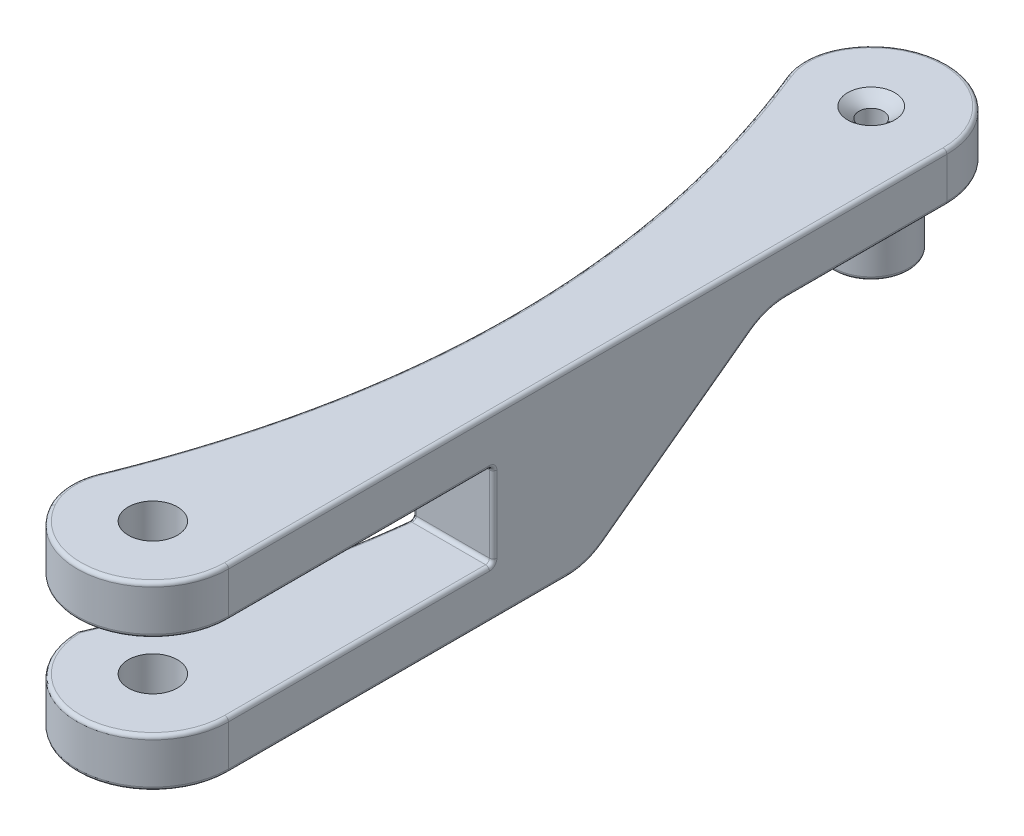
SolidWorks part; units mm, degrees
ref_plane "Front Plane" through (0, 0, 0) normal (0, 0, 1) x (1, 0, 0)
ref_plane "Top Plane" through (0, 0, 0) normal (0, 1, 0) x (1, 0, 0)
ref_plane "Right Plane" through (0, 0, 0) normal (1, 0, 0) x (0, 0, -1)
sketch "Sketch2" plane through (0, 0, 0) normal (0, 1, 0) x (1, 0, 0)
  line L0 (0, 0) -> (0, -95) construction
  line L1 (10, 0) -> (10, -95)
  line L2 (-10, 0) -> (-10, -95)
  arc A0 (10, 0) -> (-10, 0) centre (0, 0) ccw
  arc A1 (-10, -95) -> (10, -95) centre (0, -95) ccw
  circle A2 centre (0, 0) radius 1.625
  circle A3 centre (0, -95) radius 3.25
  point P3 (0, -47.5)
  dimension "D2" = 20
  dimension "D3" = 3.25
  dimension "D4" = 6.5
  dimension "D1" = 95
extrude "Boss-Extrude1" add sketch "Sketch2" along normal blind 16.5
sketch "Sketch3" plane through (0, 0, 0) normal (0, -1, 0) x (1, 0, 0)
  circle A0 centre (0, 0) radius 3.125
  dimension "D1" = 6.25
extrude "Cut-Extrude1" cut sketch "Sketch3" against normal blind 4.25
sketch "Sketch5" plane through (0, 0, 0) normal (0, -1, 0) x (1, 0, 0)
  line L0 (-10, 0) -> (-10, 47.5)
  line L1 (-10, 0) -> (-10, 95) construction
  line L2 (-10, 47.5) -> (10, 47.5)
  line L4 (10, 47.5) -> (10, 0)
  line L5 (10, 95) -> (10, 0) construction
  arc A0 (-10, 0) -> (10, 0) centre (0, 0) ccw
  arc A1 (-10, 0) -> (10, 0) centre (0, 0) ccw construction
  circle A2 centre (0, 0) radius 5
  dimension "D1" = 10
extrude "Cut-Extrude3" cut sketch "Sketch5" against normal blind 10.1
sketch "Sketch10" plane through (0, 0, 0) normal (0, -1, 0) x (1, 0, 0)
  line L0 (-10, 47.5) -> (10, 47.5)
  line L5 (-10, 47.5) -> (-10, 95)
  line L6 (10, 95) -> (10, 47.5)
  line L7 (-10, 47.5) -> (-10, 95)
  line L8 (10, 95) -> (10, 47.5)
  circle A1 centre (0, 95) radius 3.25
  arc A2 (10, 95) -> (-10, 95) centre (0, 95) ccw
  arc A3 (10, 95) -> (-10, 95) centre (0, 95) ccw
  circle A4 centre (0, 95) radius 3.25 construction
  dimension "D1" = 0
extrude "Boss-Extrude3" add sketch "Sketch10" along normal blind 7.4
sketch "Sketch8" plane through (10, 0, 0) normal (1, 0, 0) x (0, 0, -1)
  line L0 (-47.5, -7.4) -> (-23.75, 10.1)
  line L1 (0, 10.1) -> (-47.5, 10.1) construction
  line L2 (-23.75, 10.1) -> (-47.5, 10.1)
  line L3 (-47.5, 10.1) -> (-47.5, -7.4)
extrude "Boss-Extrude2" add sketch "Sketch8" against normal up to surface (20 mm away) up to face at (-10, 6.4, 47.5)
sketch "Sketch4" plane through (0, 16.5, 0) normal (0, 1, 0) x (1, 0, 0)
  line L0 (-10, 0) -> (-10, -95) construction
  line L1 (-10, 0) -> (-10, -95)
  spline S0 degree 2 poles (-10, 0) (10, -47.5) (-10, -95) knots 0 0 0 1 1 1
  point P8 (-10, -47.5)
extrude "Cut-Extrude2" cut sketch "Sketch4" against normal through all
sketch "Sketch9" plane through (0, 0, 0) normal (1, 0, 0) x (0, 0, -1)
  line L0 (-105, 16.5) -> (-105, -7.4) construction
  line L1 (-105, 10.1) -> (-60, 10.1)
  line L2 (-105, 10.1) -> (-105, -1)
  line L3 (-105, -1) -> (-60, -1)
  line L4 (-60, 10.1) -> (-60, -1)
  point P4 (-105, 4.55)
  dimension "D1" = 11.1
  dimension "D2" = 45
extrude "Cut-Extrude4" cut sketch "Sketch9" against normal through all both and the other way through all
fillet "Fillet1" radius 8 4 edges at (-10, 13.3, 95) (3.75, 10.1, 23.75) (5, -7.4, 47.5)
fillet "Fillet2" radius 0.5 33 edges at (10, 4.55, 60) (10, 10.1, 77.5) (2.5098, 10.1, 104.6799) (-9.7326, 10.1, 96.4681) (-0.6925, 4.55, 60) (4.6537, 10.1, 60) (0, -1, 105) (10, -1, 77.5) (4.6537, -1, 60) (10, 1.35, 35.625) (10, 9.7001, 23.6186) (10, 10.1, 10.5605) (-9.7326, 10.1, -1.4681) (-2.4894, 9.6379, 23.8005) (-9.7326, 16.5, 96.4681) (2.5098, 16.5, 104.6799) (10, 16.5, 47.5) (2.5098, 16.5, -9.6799) (-9.7326, 16.5, -1.4681) (0, -7.4, 105) (10, -7.4, 72.5645) (10, -7.0001, 47.6314) (-0.0003, -7.0469, 47.7785) (0, 10.1, -5) (0, 0, -3.125) (0, 0, -5)
ref_plane "Plane1" through (0, 8.25, 0) normal (0, 1, 0) x (1, 0, 0)
sketch "Sketch11" plane through (0, 16.5, 0) normal (0, 1, 0) x (1, 0, 0)
  circle A0 centre (0, 0) radius 3.125
  dimension "D1" = 6.25
ref_plane "Plane2" through (0, 14, 0) normal (0, 1, 0) x (1, 0, 0)
sketch "Sketch12" plane through (0, 14, 0) normal (0, 1, 0) x (1, 0, 0)
  circle A0 centre (0, 0) radius 1.625
  circle A1 centre (0, 0) radius 1.625
loft "Cut-Loft1" cut profiles "Sketch12", "Sketch11" connector at (-1.6223, 14, -0.0929) connector at (0, 16.5, 3.125)
